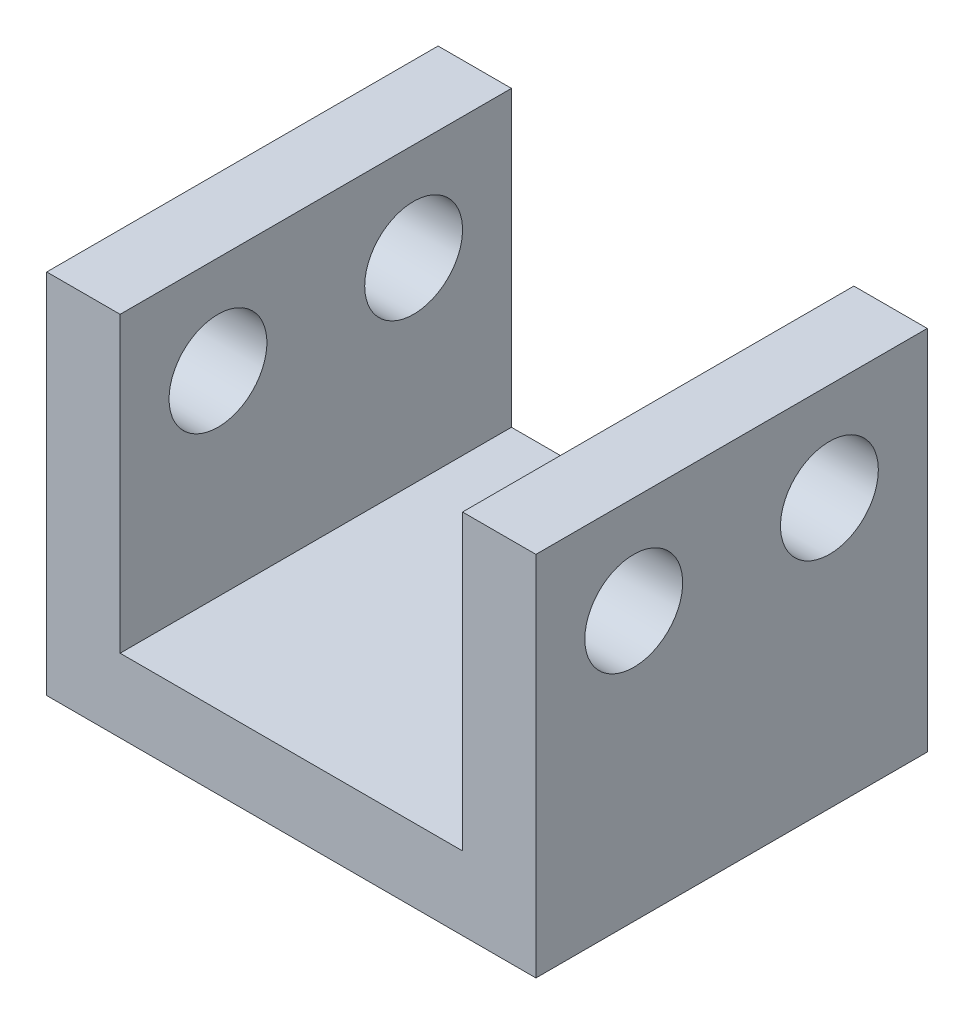
SolidWorks part; units mm, degrees
ref_plane "Front Plane" through (0, 0, 0) normal (0, 0, 1) x (1, 0, 0)
ref_plane "Top Plane" through (0, 0, 0) normal (0, 1, 0) x (1, 0, 0)
ref_plane "Right Plane" through (0, 0, 0) normal (1, 0, 0) x (0, 0, -1)
sketch "Sketch1" plane through (0, 0, 0) normal (0, 1, 0) x (1, 0, 0)
  line L1 (-5, -4) -> (5, -4)
  line L2 (-5, -4) -> (-5, 4)
  line L3 (-5, 4) -> (5, 4)
  line L4 (5, -4) -> (5, 4)
  line L5 (-5, -4) -> (5, 4) construction
  line L6 (-5, 4) -> (5, -4) construction
  point P0 (0, 0)
  dimension "D1" = 10
  dimension "D2" = 8
extrude "Boss-Extrude1" add sketch "Sketch1" along normal blind 1.5
sketch "Sketch3" plane through (0, 1.5, 0) normal (0, 1, 0) x (1, 0, 0)
  line L0 (-5, -4) -> (5, -4) construction
  line L1 (-5, 4) -> (-3.5, 4)
  line L2 (-5, 4) -> (-5, -4)
  line L3 (-5, -4) -> (-3.5, -4)
  line L4 (-3.5, 4) -> (-3.5, -4)
  line L5 (0, 4) -> (0, -4) construction
  line L6 (3.5, 4) -> (3.5, -4)
  line L7 (5, -4) -> (3.5, -4)
  line L8 (5, 4) -> (5, -4)
  line L9 (5, 4) -> (3.5, 4)
  point P11 (0, 0)
  dimension "D1" = 1.5
extrude "Boss-Extrude2" add sketch "Sketch3" along normal blind 6
sketch "Sketch4" plane through (0, 1.5, 0) normal (0, 1, 0) x (1, 0, 0)
  circle A0 centre (0, 1.7347) radius 1.85 construction
  circle A1 centre (0, 1.7347) radius 1.85 construction
  circle A2 centre (0, 1.7347) radius 1.2
  dimension "D1" = 2.4
extrude "Cut-Extrude1" cut sketch "Sketch4" against normal through all
sketch "Sketch5" plane through (-5, 0, 0) normal (-1, 0, 0) x (0, 0, 1)
  line L0 (4, 5.5) -> (-4, 5.5) construction
  line L1 (4, 7.5) -> (4, 0) construction
  line L2 (-4, 7.5) -> (-4, 0) construction
  line L3 (2, 7.5) -> (2, 5.5) construction
  line L4 (-4, 7.5) -> (4, 7.5) construction
  circle A0 centre (2, 5.5) radius 1
  dimension "D3" = 2
  dimension "D1" = 2
  dimension "D2" = 2
extrude "Cut-Extrude2" cut sketch "Sketch5" against normal through all
mirror "Mirror1" about plane through (0, 0, 0) normal (0, 0, 1) of "Cut-Extrude2"
